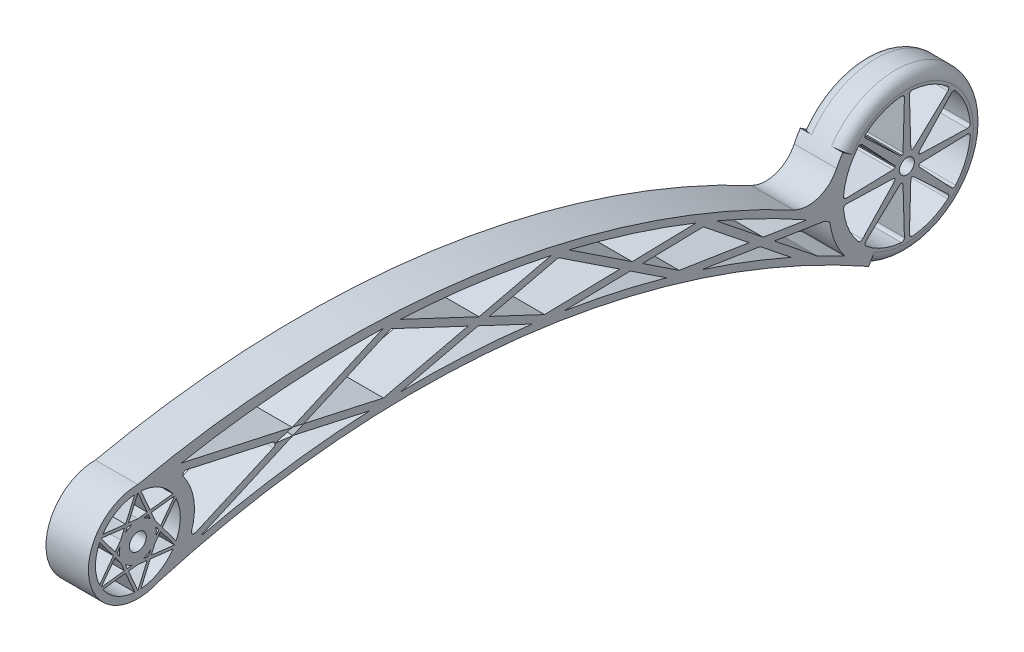
SolidWorks part; units mm, degrees
material "ABS"
ref_plane "Płaszczyzna przednia" through (0, 0, 0) normal (0, 0, 1) x (1, 0, 0)
ref_plane "Płaszczyzna górna" through (0, 0, 0) normal (0, 1, 0) x (1, 0, 0)
ref_plane "Płaszczyzna prawa" through (0, 0, 0) normal (1, 0, 0) x (0, 0, -1)
sketch "Szkic1" plane through (0, 0, 0) normal (1, 0, 0) x (0, 0, -1)
  line L11 (54.596, 25.632) -> (86.712, 39.8517)
  line L12 (58.7146, 24.7214) -> (86.848, 18.5017)
  line L13 (21.9483, 8.4427) -> (54.8577, 23.0137)
  line L14 (14.2088, 32.0004) -> (50.7391, 23.9243)
  line L15 (18.133, 9.4875) -> (50.7391, 23.9243)
  line L16 (15.3713, 34.3038) -> (54.596, 25.632)
  line L17 (58.7146, 24.7214) -> (89.5507, 38.3745)
  line L18 (54.8577, 23.0137) -> (81.9946, 17.0143)
  line L19 (124.3011, 24.762) -> (143.8506, 15.5491)
  line L20 (120.668, 26.4741) -> (146.1803, 32.488)
  line L21 (120.3919, 23.8405) -> (139.5065, 14.8326)
  line L22 (124.3011, 24.762) -> (148.7435, 30.5237)
  line L23 (89.5507, 38.3745) -> (116.7588, 25.5526)
  line L24 (150.7937, 13.2107) -> (174.1254, 13.7558)
  line L25 (200.0076, 14.3606) -> (216.1837, 1.3959)
  line L26 (92.9665, 17.3755) -> (120.3919, 23.8405)
  line L27 (148.7435, 30.5237) -> (170.4693, 16.1711)
  line L28 (199.4355, 1.51) -> (220.1167, -1.7563)
  line L29 (92.8118, 39.6014) -> (120.668, 26.4741)
  line L30 (143.8506, 15.5491) -> (170.4693, 16.1711)
  line L31 (204.6, 13.8838) -> (221.1623, 0.6096)
  line L32 (86.848, 18.5017) -> (116.7588, 25.5526)
  line L33 (152.4856, 31.0479) -> (174.8499, 16.2734)
  line L34 (191.4595, 5.3007) -> (216.1837, 1.3959)
  line L35 (174.1254, 13.7558) -> (186.9931, 5.255)
  line L36 (174.8499, 16.2734) -> (197.5033, 16.8027)
  line L37 (178.5059, 13.8582) -> (191.4595, 5.3007)
  line L38 (178.5059, 13.8582) -> (200.0076, 14.3606)
  line L39 (221.1623, 0.6096) -> (236.6131, -1.8307)
  line L40 (220.1167, -1.7563) -> (231.0391, -10.5102)
  line L41 (225.0952, -2.5426) -> (240.3985, -14.8077)
  line L42 (225.0952, -2.5426) -> (242.6899, -5.3214)
  circle A0 centre (0, 17.9252) radius 17.5
  circle A1 centre (0, 17.9252) radius 3
  arc A2 (244.5117, -3.4071) -> (0, 35.4252) centre (72.3468, -298.2483) ccw
  arc A3 (236.7304, -15.8386) -> (7.1155, 1.9371) centre (98.3142, -311.9128) ccw construction
  circle A4 centre (272.0097, -3.0749) radius 27.5
  arc A5 (244.7278, -6.5311) -> (8.876, 33.0072) centre (76.3157, -287.9196) ccw
  arc A6 (258.529, -27.0441) -> (7.1155, 1.9371) centre (98.3142, -311.9128) ccw
  arc A7 (250.0383, -19.613) -> (12.9603, 6.166) centre (98.3142, -311.9128) ccw
  arc A8 (16.8751, 7.1907) -> (12.2878, 33.7053) centre (0, 17.9252) ccw
  arc A9 (237.7892, -13.5739) -> (6.4179, 4.3378) centre (98.3142, -311.9128) ccw construction
  arc A10 (231.9153, 3.596) -> (247.1439, 8.6699) centre (237.1044, 13.4118) ccw
  circle A11 centre (0, 17.9252) radius 20 construction
  point P3 (206.3115, -91.4332)
  point P7 (210.9875, -66.8744)
  point P10 (222.3945, 17.8256)
  point P11 (200.4339, 25.8186)
  point P12 (188.4632, -7.0706)
  point P21 (193.8769, -58.5267)
  point P22 (187.3305, -92.9091)
  point P23 (210.2881, -97.2801)
  point P24 (216.8345, -62.8978)
  point P27 (210.4238, -15.0636)
  point P30 (207.4354, -8.655)
  point P31 (215.9859, 14.8373)
  point P43 (20, 17.9252)
  point P50 (242.3808, -10.2063)
  dimension "D5" = 327.9362
  dimension "D2" = 2.5
  dimension "D7" = 2.5
  dimension "D9" = 6
  dimension "D10" = 35
  dimension "D17" = 72.3468
  dimension "D3" = 341.4265
  dimension "D4" = 55
  dimension "D6" = 326.8317
  dimension "D15" = 8.876
  dimension "D12" = 7.1155
  dimension "D14" = 98.3142
  dimension "D16" = 12.2878
  dimension "D18" = 1.9371
  dimension "D22" = 242.3808
extrude "Dodanie-wyciągnięcie1" add sketch "Szkic1" along normal blind 15 contours A5 A2 A0 | A7 A0 A6 | A5 L39 L31 L36 L33 L20 L29 L11 L16 A8 L14 L15 A7 L13 L18 L26 L21 L24 L35 L28 L40 L41 L42 L32 L12 L17 L23 L30 L19 L22 L27 L37 L38 L25 L34 | A0 A1 | A8 A5 A0 A7 | A2 | A6 | A4 region at (0, 30.5766, -71.6127) region at (0, 41.5191, -50.6962) region at (0, 32.6615, -13.0786) region at (0, 26.3663, -14.7621) region at (0, 6.4374, -14.9808) region at (0, 1.305, -241.7606) region at (0, -3.0749, -272.0097)
sketch "Szkic2" plane through (15, 0, 0) normal (1, 0, 0) x (0, 0, -1)
  line L0 (-8.0458, 18.7641) -> (-6.0679, 21.4286)
  line L1 (-7.4231, 17.9252) -> (-6.356, 19.3628)
  line L2 (-7.4231, 17.9252) -> (-6.356, 16.4877)
  line L3 (-12.9904, 10.4252) -> (-5.1962, 20.9252) construction
  line L4 (-8.0458, 17.0864) -> (-6.0679, 14.4219)
  line L5 (-12.9904, 25.4252) -> (-5.1962, 14.9252) construction
  line L6 (0, 32.9252) -> (-3.2964, 25.3125)
  line L7 (0, 32.9252) -> (3.2964, 25.3125)
  line L8 (12.9904, 25.4252) -> (4.7494, 24.4736)
  line L9 (12.9904, 25.4252) -> (8.0458, 18.7641)
  line L10 (12.9904, 10.4252) -> (8.0458, 17.0864)
  line L11 (12.9904, 10.4252) -> (4.7494, 11.3768)
  line L12 (0, 2.9252) -> (3.2964, 10.5379)
  line L13 (0, 2.9252) -> (-3.2964, 10.5379)
  line L14 (-12.9904, 10.4252) -> (-4.7494, 11.3768)
  line L15 (-12.9904, 10.4252) -> (-8.0458, 17.0864)
  line L16 (-12.9904, 25.4252) -> (-8.0458, 18.7641)
  line L17 (-12.9904, 25.4252) -> (-4.7494, 24.4736)
  line L18 (0, 35.4418) -> (0.0072, 35.4252)
  line L19 (0, 35.4418) -> (-0.0072, 35.4252)
  line L20 (-15.1698, 9.1669) -> (-15.159, 9.1815)
  line L21 (-15.1698, 9.1669) -> (-15.1518, 9.169)
  line L22 (-4.7494, 24.4736) -> (-6.0679, 21.4286)
  line L23 (-3.2964, 25.3125) -> (0, 24.9319)
  line L24 (-3.7115, 24.3538) -> (-1.933, 24.1484)
  line L25 (-3.7115, 24.3538) -> (-4.4229, 22.7109)
  line L26 (-12.9904, 25.4252) -> (0, 23.9252) construction
  line L27 (3.7115, 24.3538) -> (4.4229, 22.7109)
  line L28 (-3.7115, 11.4967) -> (-1.933, 11.702)
  line L29 (-1.1075, 2.9662) -> (-4.3342, 10.4181)
  line L30 (-15.1698, 26.6835) -> (-15.159, 26.669)
  line L31 (-15.1698, 26.6835) -> (-15.1518, 26.6815)
  line L32 (1.1075, 2.9662) -> (4.3342, 10.4181)
  line L33 (0, 32.9252) -> (-5.1962, 20.9252) construction
  line L34 (-4.7494, 11.3768) -> (-6.0679, 14.4219)
  line L35 (-12.9904, 10.4252) -> (0, 11.9252) construction
  line L36 (15.1698, 9.1669) -> (15.159, 9.1815)
  line L37 (15.1698, 9.1669) -> (15.1518, 9.169)
  line L38 (15.1698, 26.6835) -> (15.159, 26.669)
  line L39 (15.1698, 26.6835) -> (15.1518, 26.6815)
  line L40 (7.4231, 17.9252) -> (6.356, 16.4877)
  line L41 (3.2964, 25.3125) -> (0, 24.9319)
  line L42 (-13.5087, 24.4457) -> (-8.6685, 17.9252)
  line L43 (-12.4012, 26.3638) -> (-4.3342, 25.4323)
  line L44 (-15.1698, 26.6835) -> (-6.0679, 14.4219) construction
  line L45 (-1.1075, 32.8843) -> (-4.3342, 25.4323)
  line L46 (-15.1698, 26.6835) -> (0.1147, 24.9186) construction
  line L47 (1.1075, 32.8843) -> (4.3342, 25.4323)
  line L48 (0, 35.4418) -> (-6.0679, 21.4286) construction
  line L49 (12.4012, 26.3638) -> (4.3342, 25.4323)
  line L50 (0, 35.4418) -> (6.1138, 21.3226) construction
  line L51 (13.5087, 24.4457) -> (8.6685, 17.9252)
  line L52 (15.1698, 26.6835) -> (-0.1147, 24.9186) construction
  line L53 (13.5087, 11.4048) -> (8.6685, 17.9252)
  line L54 (15.1698, 26.6835) -> (5.9991, 14.3292) construction
  line L55 (12.4012, 9.4866) -> (4.3342, 10.4181)
  line L56 (15.1698, 9.1669) -> (5.9991, 21.5213) construction
  line L57 (-12.4012, 9.4866) -> (-4.3342, 10.4181)
  line L58 (15.1698, 9.1669) -> (-0.1147, 10.9318) construction
  line L59 (-0.9177, 2.5279) -> (-6.0679, 14.4219) construction
  line L60 (-13.5087, 11.4048) -> (-8.6685, 17.9252)
  line L61 (-15.1698, 9.1669) -> (0.1147, 10.9318) construction
  line L62 (-3.7115, 11.4967) -> (-4.4229, 13.1396)
  line L63 (-15.1698, 9.1669) -> (-6.0679, 21.4286) construction
  line L64 (0.9177, 2.5279) -> (6.1138, 14.5279) construction
  line L65 (-3.2964, 10.5379) -> (0, 10.9186)
  line L66 (0, 32.9252) -> (5.1962, 20.9252) construction
  line L67 (8.0458, 18.7641) -> (6.0679, 21.4286)
  line L68 (12.9904, 25.4252) -> (5.1962, 14.9252) construction
  line L69 (4.7494, 24.4736) -> (6.0679, 21.4286)
  line L70 (0, 2.9252) -> (-5.1962, 14.9252) construction
  line L71 (3.7115, 11.4967) -> (4.4229, 13.1396)
  line L72 (3.7115, 24.3538) -> (1.933, 24.1484)
  line L73 (8.0458, 17.0864) -> (6.0679, 14.4219)
  line L74 (3.7115, 11.4967) -> (1.933, 11.702)
  line L75 (0, 2.9252) -> (5.1962, 14.9252) construction
  line L76 (12.9904, 25.4252) -> (0, 23.9252) construction
  line L77 (3.2964, 10.5379) -> (0, 10.9186)
  line L78 (7.4231, 17.9252) -> (6.356, 19.3628)
  line L79 (12.9904, 10.4252) -> (0, 11.9252) construction
  line L80 (12.9904, 10.4252) -> (5.1962, 20.9252) construction
  line L81 (4.7494, 11.3768) -> (6.0679, 14.4219)
  line L82 (-6.0679, 21.4286) -> (-5.6435, 21.1835) construction
  circle A1 centre (0, 17.9252) radius 17.5
  circle A2 centre (0, 17.9252) radius 15
  circle A3 centre (0, 17.9252) radius 6.5165
  point P5 (-0.2017, 28.9866)
  point P6 (-0.2017, 28.9866)
  point P7 (6.1719, 28.9866)
  point P9 (-0.2017, 33.3602)
  point P31 (0.9177, 3.3226)
  point P33 (-4.3244, 15.4286)
  point P34 (-10.8109, 24.1669)
  point P36 (-0.1147, 22.9318)
  point P37 (0, 30.4086)
  point P38 (4.2785, 20.5279)
  point P39 (-4.3244, 20.4219)
  point P40 (-10.8109, 11.6835)
  point P41 (-0.1147, 12.9186)
  point P48 (10.8109, 11.6835)
  point P49 (4.3932, 20.3292)
  point P50 (0.1147, 12.9186)
  point P51 (-0.9177, 3.3226)
  point P52 (4.2785, 15.3226)
  point P59 (10.8109, 24.1669)
  point P60 (4.3932, 15.5213)
  point P61 (0.1147, 22.9318)
  dimension "D2" = 30
  dimension "D3" = 35
  dimension "D5" = 6
extrude "Wytnij-wyciągnięcie1" cut sketch "Szkic2" against normal through all contours L22 L17 L16 L0 | L42 A2 L60 | A3 L1 L2 | A3 L24 L25 | A3 L27 L72 | A3 L40 L78 | A3 L74 L71 | A3 L62 L28 | L14 L34 L4 L15 | L41 L7 L6 L23 | L49 A2 L47 | L45 A2 L43 | L8 L69 L67 L9 | L53 A2 L51 | L81 L11 L10 L73 | L57 A2 L29 | L12 L77 L65 L13 | L32 A2 L55 region at (15, 22.8242, 8.4853) region at (15, 13.0262, 8.4853) region at (15, 8.1273, 0) region at (15, 13.0262, -8.4853) region at (15, 22.8242, -8.4853) region at (15, 27.7232, 0) region at (15, 28.7889, 6.2721) region at (15, 17.9252, 12.5443) region at (15, 28.7889, -6.2721) region at (15, 7.0616, 6.2721) region at (15, 17.9252, -12.5443) region at (15, 7.0616, -6.2721) region at (15, 17.9252, 6.785) region at (15, 23.8012, 3.3925) region at (15, 12.0492, 3.3925) region at (15, 23.8012, -3.3925) region at (15, 12.0492, -3.3925) region at (15, 17.9252, -6.785)
ref_axis "Oś1" through (15, -3.0749, -272.0097) along (-1, 0, 0)
ref_plane "Płaszczyzna1" through (0, -116.9596, -207.9591) normal (0, 0.4902, 0.8716) x (1, 0, 0)
sketch "Szkic3" plane through (0, -116.9596, -207.9591) normal (0, 0.4902, 0.8716) x (1, 0, 0)
  line L1 (15, 130.6607) -> (0, 130.6607)
  line L3 (11, 103.1607) -> (4, 103.1607)
  line L6 (15, 130.6607) -> (0, 130.6607) construction
  line L7 (0, 107.1607) -> (0, 103.1607)
  line L8 (0, 103.1607) -> (15, 103.1607)
  line L9 (15, 103.1607) -> (15, 107.1607)
  arc A0 (11, 103.1607) -> (15, 107.1607) centre (11, 107.1607) ccw
  arc A1 (4, 103.1607) -> (0, 107.1607) centre (4, 107.1607) cw
  dimension "D1" = 4
revolve "Wycięcie-obrót1" cut sketch "Szkic3" angle 265 about L1 region at (0.8935, -26.2653, -258.967) region at (14.1065, -26.2653, -258.967) reverse direction yes
sketch "Szkic4" plane through (0, 0, 0) normal (-1, 0, 0) x (0, 0, 1)
  line L0 (-272.0097, -3.0749) -> (-294.5097, -3.0749) construction
  line L1 (-294.4935, -3.9278) -> (-276.287, -4.4732)
  line L2 (-294.4935, -2.2221) -> (-276.287, -1.6766)
  line L3 (-288.5112, 12.2205) -> (-276.0229, -1.0392)
  line L4 (-287.3051, 13.4266) -> (-274.0455, 0.9383)
  line L5 (-272.8626, 19.4089) -> (-273.408, 1.2023)
  line L6 (-271.1569, 19.4089) -> (-270.6114, 1.2023)
  line L7 (-256.7143, 13.4266) -> (-269.974, 0.9383)
  line L8 (-255.5082, 12.2205) -> (-267.9965, -1.0392)
  line L9 (-249.5259, -2.2221) -> (-267.7325, -1.6766)
  line L10 (-249.5259, -3.9278) -> (-267.7325, -4.4732)
  line L11 (-255.5082, -18.3703) -> (-267.9965, -5.1107)
  line L12 (-256.7143, -19.5764) -> (-269.974, -7.0881)
  line L13 (-271.1569, -25.5587) -> (-270.6114, -7.3522)
  line L14 (-272.8626, -25.5587) -> (-273.408, -7.3522)
  line L15 (-287.3051, -19.5764) -> (-274.0455, -7.0881)
  line L16 (-288.5112, -18.3703) -> (-276.0229, -5.1107)
  circle A0 centre (-272.0097, -3.0749) radius 22.5
  circle A1 centre (-272.0097, -3.0749) radius 4.5
  circle A2 centre (-272.0097, -3.0749) radius 2.6413
  point P39 (-272.0097, -3.0749)
  dimension "D1" = 8
  dimension "D2" = 9
  dimension "D3" = 45
extrude "Wytnij-wyciągnięcie2" cut sketch "Szkic4" against normal through all contours A1 L15 A0 L14 | A1 L1 A0 L16 | A1 L3 A0 L2 | A1 L5 A0 L4 | A1 L7 A0 L6 | A1 L9 A0 L8 | A1 L11 A0 L10 | A1 L13 A0 L12 | A2 region at (0, -9.1776, -286.743) region at (0, 3.0278, -286.743) region at (0, -17.8082, -278.1124) region at (0, 11.6584, -278.1124) region at (0, -17.8082, -265.907) region at (0, 11.6584, -265.907) region at (0, -9.1776, -257.2764) region at (0, 3.0278, -257.2764) region at (0, -3.0749, -272.0097)
fillet "Zaokrąglenie2" radius 1 32 edges at (7.5, -1.0392, -267.9965) (7.5, -1.6766, -267.7325) (7.5, 12.2205, -255.5082) (7.5, -2.2221, -249.5259) (7.5, -7.0881, -269.974) (7.5, -7.3522, -270.6114) (7.5, -19.5764, -256.7143) (7.5, -4.4732, -267.7325) (7.5, -7.0881, -274.0455) (7.5, -7.3522, -273.408) (7.5, -3.9278, -249.5259) (7.5, -18.3703, -255.5082) (7.5, 19.4089, -272.8626) (7.5, -1.0392, -276.0229) (7.5, -4.4732, -276.287) (7.5, 12.2205, -288.5112) (7.5, -18.3703, -288.5112) (7.5, -25.5587, -272.8626) (7.5, -5.1107, -276.0229) (7.5, -1.6766, -276.287) (7.5, 0.9383, -274.0455) (7.5, 1.2023, -273.408) (7.5, -25.5587, -271.1569) (7.5, -19.5764, -287.3051) (7.5, 13.4266, -287.3051) (7.5, -2.2221, -294.4935) (7.5, -3.9278, -294.4935) (7.5, -5.1107, -267.9965) (7.5, 1.2023, -270.6114) (7.5, 0.9383, -269.974) (7.5, 19.4089, -271.1569) (7.5, 13.4266, -256.7143)
ref_axis "Oś2" through (15, -3.0749, -272.0097) along (-1, 0, 0)
fillet "Zaokrąglenie3" radius 1 3 edges at (7.5, 23.9243, -50.7391) (7.5, 32.0004, -14.2088) (7.5, 9.4875, -18.133)
ref_axis "Oś3" through (15, 17.9252, 0) along (-1, 0, 0)
